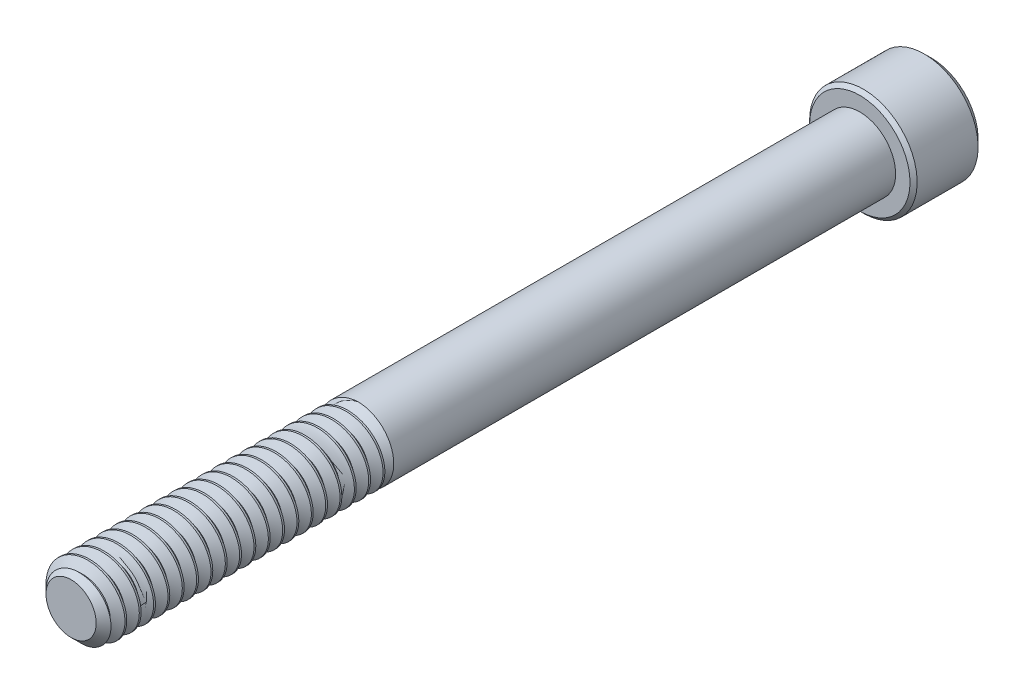
SolidWorks part; units mm, degrees
material "Cast Alloy Steel"
ref_plane "Front Plane" through (0, 0, 0) normal (0, 0, 1) x (1, 0, 0)
ref_plane "Top Plane" through (0, 0, 0) normal (0, 1, 0) x (1, 0, 0)
ref_plane "Right Plane" through (0, 0, 0) normal (1, 0, 0) x (0, 0, -1)
sketch "Sketch1" plane through (0, 0, 0) normal (0, 0, 1) x (1, 0, 0)
  line L0 (0, 3.175) -> (0, -3.175) construction
  circle A0 centre (0, 0) radius 3.175
  dimension "OD" = 6.35
extrude "Extrude1" add sketch "Sketch1" against normal blind 69.85
sketch "Sketch2" plane through (0, 0, 0) normal (0, 0, 1) x (1, 0, 0)
  circle A0 centre (0, 0) radius 3.175 construction
  circle A1 centre (0, 0) radius 3.175
curve "Helix/Spiral1" pitch 1.27 height 27.94 turns 22 parameters "pitch"=1.27
chamfer "Chamfer3" distance 0.9525 angle 45 1 edges at (3.175, 0, 0)
sketch "Sketch3" plane through (0, 0, 0) normal (1, 0, 0) x (0, 0, -1)
  line L0 (-1.1112, 3.175) -> (-0.635, 2.3501)
  line L1 (-0.635, 2.3501) -> (-0.4763, 2.3501)
  line L2 (-0.4763, 2.3501) -> (0, 3.175)
  line L3 (-1.1112, 3.175) -> (0, 3.175)
  line L4 (-0.5556, 3.175) -> (-0.5556, 2.3501) construction
  line L5 (-0.8731, 2.7626) -> (-0.2381, 2.7626) construction
  line L6 (0, 3.175) -> (0, -3.175) construction
  dimension "D1" = 0.1588
  dimension "D2" = 0.635
  dimension "D3" = 60
sweep "Cut-Sweep1" cut profiles "Sketch3" path "Helix/Spiral1"
sketch "Sketch5" plane through (0, 0, 0) normal (1, 0, 0) x (0, 0, -1)
  line L1 (69.85, 3.175) -> (25.4, 3.175)
  line L2 (69.85, 3.175) -> (69.85, 0)
  line L3 (69.85, 0) -> (25.4, 0)
  line L4 (25.4, 3.175) -> (25.4, 0) construction
  line L6 (0, 0) -> (9.9695, 0) construction
  line L8 (25.4, 3.175) -> (22.225, 0)
  line L9 (22.225, 0) -> (25.4, 0)
  line L10 (69.85, -3.175) -> (69.85, 3.175) construction
  dimension "D1" = 45
  dimension "Thread min" = 25.4
revolve "partially thread" add sketch "Sketch5" angle 360 about L6
sketch "Sketch6" plane through (0, 0, -69.85) normal (0, 0, -1) x (-1, 0, 0)
  circle A0 centre (0, 0) radius 4.7625
  dimension "head dia" = 9.525
extrude "Extrude2" add sketch "Sketch6" along normal blind 6.35
sketch "Sketch7" plane through (0, 0, -76.2) normal (0, 0, -1) x (-1, 0, 0)
  line L1 (0, 2.7496) -> (-2.3812, 1.3748)
  line L2 (-2.3812, 1.3748) -> (-2.3813, -1.3748)
  line L3 (-2.3813, -1.3748) -> (0, -2.7496)
  line L4 (0, -2.7496) -> (2.3813, -1.3748)
  line L5 (2.3813, -1.3748) -> (2.3813, 1.3748)
  line L6 (2.3813, 1.3748) -> (0, 2.7496)
  circle A0 centre (0, 0) radius 2.3813 construction
  dimension "hex dia" = 4.7625
extrude "Cut-Extrude1" cut sketch "Sketch7" against normal blind 3.5719
sketch "Sketch8" plane through (0, 0, -76.2) normal (0, 0, -1) x (-1, 0, 0)
  circle A0 centre (0, 0) radius 2.7496
extrude "Cut-Extrude2" cut sketch "Sketch8" against normal blind 0.635 draft 45
chamfer "Chamfer1" distance 0.635 angle 45 1 edges at (-4.7625, 0, -76.2)
chamfer "Chamfer2" distance 0.3175 angle 45 1 edges at (-4.7625, 0, -69.85)
sketch "Sketch9" plane through (0, 0, 0) normal (1, 0, 0) x (0, 0, -1)
  line L0 (0, 3.175) -> (0, -3.175) construction
  line L1 (6.985, 3.175) -> (6.985, -3.175) construction
  line L2 (69.85, 4.7625) -> (69.85, -4.7625) construction
  line L3 (76.2, 4.7625) -> (76.2, -4.7625) construction
  line L4 (76.2, 0) -> (0, 0) construction
  line L5 (61.6852, 3.175) -> (61.6852, -3.175) construction
  dimension "D1" = 6.985
  dimension "D2" = 6.35
  dimension "D3" = 9.525
  dimension "D4" = 69.85
  dimension "Thread Length" = 61.6852
equation "\"D3@Helix/Spiral1\" = \"Thread min@Sketch5\"+(\"pitch@Helix/Spiral1\"*2)"
equation "\"D1@Sketch3\" = \"pitch@Helix/Spiral1\"*.125"
equation "\"D2@Sketch3\" = \"pitch@Helix/Spiral1\"*.5"
equation "\"D1@Cut-Extrude1\" = \"hex dia@Sketch7\"*.75"
equation "\"D1@Chamfer1\" = \"head depth@Extrude2\"/10"
equation "\"D1@Sketch9\" = \"pitch@Helix/Spiral1\"*5.5"
equation "\"D1@Chamfer2\" = \"D1@Chamfer1\"/2"
equation "\"D1@Cut-Extrude2\" = \"D1@Chamfer2\"*2"
equation "\"D1@Chamfer3\" = \"pitch@Helix/Spiral1\"*.750"
equation "\"D2@Sketch9\" = \"head depth@Extrude2\""
equation "\"D3@Sketch9\" = \"head dia@Sketch6\""
equation "\"D4@Sketch9\" = \"screw length@Extrude1\""
